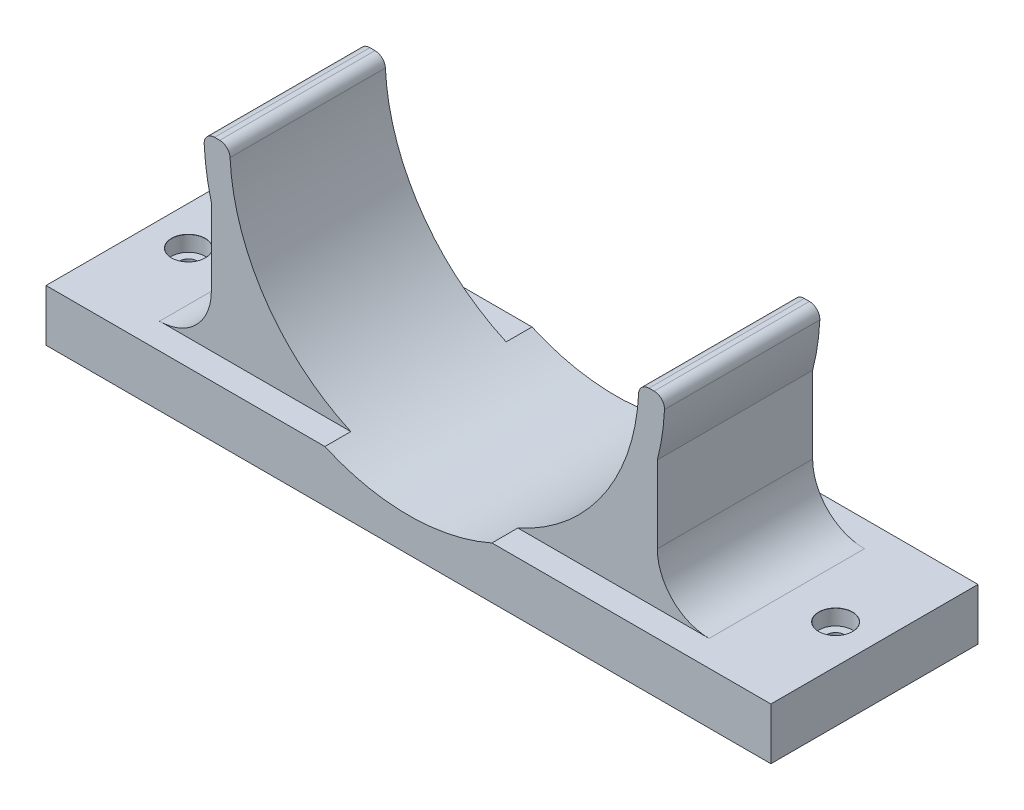
SolidWorks part; units mm, degrees
ref_plane "Front Plane" through (0, 0, 0) normal (0, 0, 1) x (1, 0, 0)
ref_plane "Top Plane" through (0, 0, 0) normal (0, 1, 0) x (1, 0, 0)
ref_plane "Right Plane" through (0, 0, 0) normal (1, 0, 0) x (0, 0, -1)
sketch "Sketch1" plane through (0, 0, 0) normal (0, 0, 1) x (1, 0, 0)
  line L2 (-70, -36.0562) -> (-16.1308, -36.0562)
  line L3 (-70, -36.0562) -> (-70, -46.0562)
  line L4 (-70, -46.0562) -> (70, -46.0562)
  line L5 (70, -36.0562) -> (70, -46.0562)
  line L6 (39.5, 0) -> (44.5, 0)
  line L7 (-70, -41.0562) -> (70, -41.0562) construction
  line L8 (16.1308, -36.0562) -> (70, -36.0562)
  line L9 (-43.0654, -36.0562) -> (-43.0654, -11.2081)
  line L10 (43.0654, -36.0562) -> (43.0654, -11.2081)
  line L12 (-39.5, 0) -> (-44.5, 0)
  line L13 (0, -39.5) -> (0, -46.0562) construction
  line L14 (-44.2182, 5) -> (44.2182, 5) construction
  line L15 (-39.5, 0) -> (39.5, 0) construction
  arc A0 (-39.5, 0) -> (39.5, 0) centre (0, 0) ccw
  arc A1 (-44.5, 0) -> (-26.0807, -36.0562) centre (0, 0) ccw
  arc A2 (26.0807, -36.0562) -> (44.5, 0) centre (0, 0) ccw
  arc A3 (-44.2182, 5) -> (44.2182, 5) centre (0, 0) ccw construction
  dimension "D1" = 140
  dimension "D2" = 10
  dimension "D3" = 5
extrude "Boss-Extrude3" add sketch "Sketch1" along normal blind 20 and the other way blind 20 contours A0 L2 L3 L4 L5 L8 region at (0, -41.2602, 0)
extrude "Boss-Extrude4" add sketch "Sketch1<6>" along normal blind 15 and the other way blind 15 contours L12 A1 L2 A0 | L8 A2 L6 A0 region at (-34.8305, -19.8543, 0) region at (34.8305, -19.8543, 0)
sketch "Sketch1<6>" plane through (0, 0, 0) normal (0, 0, 1) x (1, 0, 0) same geometry as "Sketch1"
extrude "Boss-Extrude5" add sketch "Sketch1<7>" along normal blind 15 and the other way blind 15 contours A2 L8 L10 | A1 L9 L2 region at (-38.0609, -28.9614, 0) region at (38.0609, -28.9614, 0)
sketch "Sketch1<7>" plane through (0, 0, 0) normal (0, 0, 1) x (1, 0, 0) same geometry as "Sketch1"
fillet "Fillet1" radius 10 2 edges at (43.0654, -36.0562, 0) (-43.0654, -36.0562, 0)
sketch "Sketch2" plane through (0, -36.0562, 0) normal (0, 1, 0) x (1, 0, 0)
  line L0 (62.5, 0) -> (70, 0) construction
  line L1 (-70, 20) -> (70, 20)
  line L2 (-70, 20) -> (-70, -20)
  line L3 (-70, -20) -> (70, -20)
  line L4 (70, 20) -> (70, -20)
  line L5 (-70, 0) -> (-62.5, 0) construction
  line L6 (62.5, 20) -> (62.5, -20) construction
  line L7 (-62.5, 20) -> (-62.5, -20) construction
  point P16 (-62.5, 20)
  point P17 (-62.5, 0)
  point P18 (-62.5, -20)
  dimension "D1" = 7.5
sketch "Sketch5" plane through (0, -36.0562, 0) normal (0, 1, 0) x (1, 0, 0)
  point P0 (-62.5, 0)
  point P3 (62.5, 0)
hole_wizard "CBORE for M3 SHCS1" positions "Sketch5" profile "Sketch4" counterbore size "M3" standard "ANSI Metric" end condition through all
sketch "Sketch4" plane through (-62.5, -36.0562, 0) normal (1, 0, 0) x (0, 0, 1)
  line L0 (0, 0) -> (0, 10)
  line L1 (0, 10) -> (1.7, 10)
  line L3 (1.7, 10) -> (1.7, 3)
  line L4 (3.25, 3) -> (1.7, 3)
  line L5 (3.25, 3) -> (3.25, 0.025)
  line L6 (3.25, 0.025) -> (3.275, 0)
  line L7 (3.275, 0) -> (0, 0)
  line L8 (-3.25, 0.025) -> (-3.275, 0) construction
  line L11 (0, -6.35) -> (0, 107.95) construction
  dimension "Thru Hole Dia." = 3.4
  dimension "Thru Hole Depth" = 10
  dimension "C'Bore Dia." = 6.5
  dimension "C'Bore Depth" = 3
  dimension "Near C'Sink Dia." = 6.55
  dimension "Near C'Sink Angle" = 90
fillet "Fillet2" radius 2 4 edges at (-44.5, 0, 0) (-39.5, 0, 0) (44.5, 0, 0) (39.5, 0, 0)
